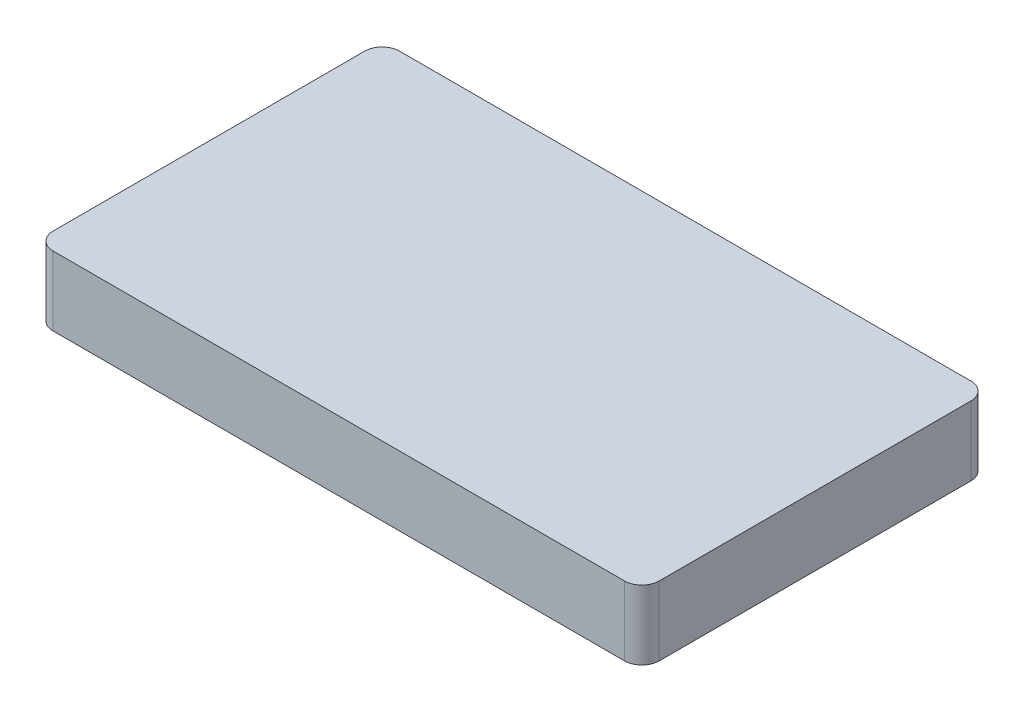
SolidWorks part; units mm, degrees
ref_plane "Front Plane" through (0, 0, 0) normal (0, 0, 1) x (1, 0, 0)
ref_plane "Top Plane" through (0, 0, 0) normal (0, 1, 0) x (1, 0, 0)
ref_plane "Right Plane" through (0, 0, 0) normal (1, 0, 0) x (0, 0, -1)
sketch "Sketch1" plane through (0, 0, 0) normal (0, 1, 0) x (1, 0, 0)
  line L0 (0, 0) -> (22.225, 0)
  line L1 (22.225, 0) -> (22.225, 12.7)
  line L2 (22.225, 12.7) -> (0, 12.7)
  line L3 (0, 12.7) -> (0, 0)
  dimension "D1" = 22.225
  dimension "D2" = 12.7
extrude "Boss-Extrude1" add sketch "Sketch1" along normal blind 2.54
fillet "Fillet1" radius 0.635 4 edges at (0, 1.27, -12.7) (22.225, 1.27, -12.7) (22.225, 1.27, 0) (0, 1.27, 0)
shell "Shell1" thickness 0.635 removed face at (11.1125, 0, -6.35)
sketch "Sketch2" plane through (0, 1.905, 0) normal (0, -1, 0) x (-1, 0, 0)
  line L0 (-0.635, 6.35) -> (-21.59, 6.35) construction
  line L1 (-0.635, 12.065) -> (-0.635, 0.635) construction
  line L2 (-21.59, 0.635) -> (-21.59, 12.065) construction
  line L3 (-11.1125, 0.635) -> (-11.1125, 12.065) construction
  line L4 (-0.635, 0.635) -> (-21.59, 0.635) construction
  line L5 (-21.59, 12.065) -> (-0.635, 12.065) construction
  circle A0 centre (-11.1125, 6.35) radius 2.54
  dimension "D1" = 5.08
extrude "Boss-Extrude2" add sketch "Sketch2" along normal up to surface (1.905 mm away) up to face at (11.1125, 0, -6.35)
